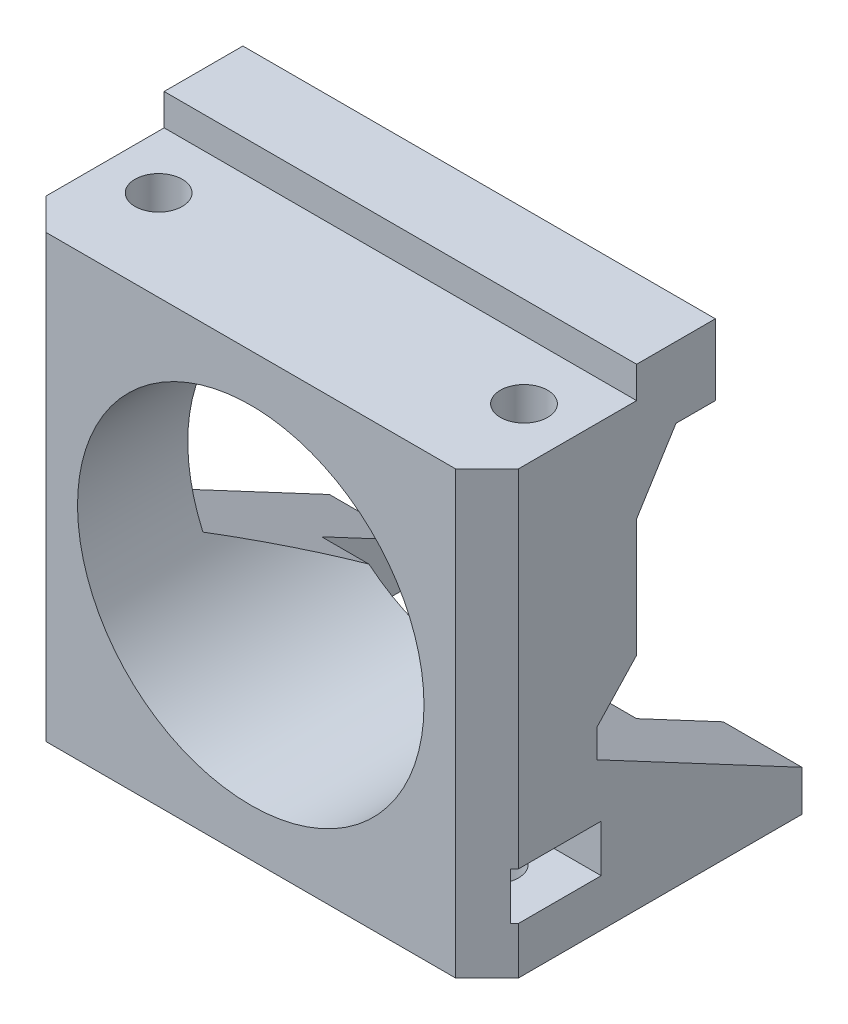
SolidWorks part; units mm, degrees
ref_plane "Front Plane" through (0, 0, 0) normal (0, 0, 1) x (1, 0, 0)
ref_plane "Top Plane" through (0, 0, 0) normal (0, 1, 0) x (1, 0, 0)
ref_plane "Right Plane" through (0, 0, 0) normal (1, 0, 0) x (0, 0, -1)
sketch "Sketch1" plane through (0, 0, 0) normal (0, 0, 1) x (1, 0, 0)
  line L1 (-15, 14) -> (15, 14)
  line L2 (-15, 14) -> (-15, -14)
  line L3 (-15, -14) -> (15, -14)
  line L4 (15, 14) -> (15, -14)
  line L5 (-15, 14) -> (15, -14) construction
  line L6 (-15, -14) -> (15, 14) construction
  circle A0 centre (0, 0) radius 11
  dimension "D1" = 22
  dimension "D2" = 30
  dimension "D3" = 28
extrude "Boss-Extrude1" add sketch "Sketch1" along normal blind 7
sketch "Sketch2" plane through (0, 0, 0) normal (0, 0, -1) x (-1, 0, 0)
  line L0 (0, 0) -> (0, -50000) construction
  line L1 (-15, -14) -> (-10, -14)
  line L2 (-15, -14) -> (-15, -11.5)
  line L3 (-15, -11.5) -> (-10, -11.5)
  line L4 (-10, -14) -> (-10, -11.5)
  line L5 (15, -11.5) -> (10, -11.5)
  line L6 (10, -14) -> (10, -11.5)
  line L7 (15, -14) -> (10, -14)
  line L8 (15, -14) -> (15, -11.5)
  dimension "D1" = 2.5
  dimension "D2" = 5
extrude "Boss-Extrude2" add sketch "Sketch2" along normal blind 13 contours L5 L6 L7 L8 | L2 L3 L4 L1
chamfer "Chamfer2" distance 2 angle 45 2 edges at (-10, -12.75, 0) (10, -12.75, 0)
sketch "Sketch5" plane through (0, -14, 0) normal (0, -1, 0) x (1, 0, 0)
  line L0 (-10, -7.5) -> (10, -7.5)
  line L1 (-10, -13) -> (-10, -2) construction
  line L2 (10, -13) -> (10, -2) construction
  line L3 (10, -7.5) -> (10, -2)
  line L4 (10, -2) -> (8, 0)
  line L5 (8, 0) -> (-8, 0)
  line L6 (-8, 0) -> (-10, -2)
  line L7 (-10, -2) -> (-10, -7.5)
  line M5 (-10, -13) -> (-10, -2)
  line M6 (-10, -2) -> (-8, 0)
  line M7 (-8, 0) -> (8, 0)
  line M8 (8, 0) -> (10, -2)
  line M9 (10, -2) -> (10, -13)
extrude "Boss-Extrude6" add sketch "Sketch5" against normal up to surface (2.5 mm away) contours L0 M5 M9 M8 M7 M6 region at (0, -14, -3.8345) up to face at (11.6, -11.5, -5.6)
chamfer "Chamfer3" distance 2 angle 45 1 edges at (15, 0, 7)
chamfer "Chamfer4" distance 2 angle 45 1 edges at (-15, 0, 7)
sketch "Sketch4" plane through (0, 0, 0) normal (0, 0, -1) x (-1, 0, 0)
  line L1 (-15, -11.5) -> (-15, 14) construction
  line L2 (-15, 14) -> (15, 14) construction
  line L3 (15, 14) -> (15, -11.5) construction
  line L8 (0, 0) -> (0, 50000) construction
  line L14 (-15, 0) -> (15, 11.5)
  line L15 (15, 11.5) -> (15, 14)
  line L16 (15, 14) -> (-15, 14)
  line L18 (-15, 14) -> (-15, 0)
  line L19 (-15, 14) -> (-15, -14) construction
  point P8 (-15, 0)
  dimension "D1" = 2.5
extrude "Boss-Extrude4" add sketch "Sketch4" along normal blind 2.5
chamfer "Chamfer6" distance 2.5 2 edges at (12.9432, 0.7884, 0) (-11.0214, 9.9749, 0)
chamfer "Chamfer7" distance 7 angle 62 1 edges at (0, -11.5, 0) first distance on face at (-0.4851, -4.0745, 0)
sketch "Sketch7" plane through (0, -14, 0) normal (0, -1, 0) x (1, 0, 0)
  circle A0 centre (11, 2.5) radius 2 construction
  circle A1 centre (-11, 2.5) radius 2 construction
  circle A2 centre (11, 2.5) radius 2 construction
  circle A3 centre (-11, 2.5) radius 2 construction
  circle A4 centre (-11, 2.5) radius 1.5
  circle A5 centre (11, 2.5) radius 1.5
  dimension "D1" = 3
  dimension "D2" = 3
extrude "Cut-Extrude2" cut sketch "Sketch7" against normal blind 6.4
sketch "Sketch8" plane through (0, 14, 0) normal (0, 1, 0) x (1, 0, 0)
  line L0 (-15, 2.5) -> (15, 2.5)
  line L1 (-15, -5) -> (-15, 2.5) construction
  line L2 (15, 2.5) -> (15, 7.5)
  line L3 (15, 7.5) -> (-15, 7.5)
  line L4 (-15, 7.5) -> (-15, 2.5)
  line L5 (15, -5) -> (15, 2.5) construction
  line L6 (-15, 2.5) -> (15, 2.5) construction
  dimension "D1" = 5
extrude "Boss-Extrude7" add sketch "Sketch8" along normal up to surface (4.5 mm away) from offset 2.5 offset against normal yes
chamfer "Chamfer8" distance 2.5 angle 58 1 edges at (0, 11.5, -2.5) first distance on face at (0, 11.5, -5)
sketch "Sketch9" plane through (0, -14, 0) normal (0, -1, 0) x (1, 0, 0)
  line L0 (-13, 7) -> (13, 7) construction
  line L1 (7.8246, 2.5) -> (9.4123, -0.25)
  line L2 (9.4123, -0.25) -> (12.5877, -0.25)
  line L3 (12.5877, -0.25) -> (14.1754, 2.5)
  line L4 (14.1754, 2.5) -> (12.5877, 5.25)
  line L5 (12.5877, 5.25) -> (9.4123, 5.25)
  line L6 (9.4123, 5.25) -> (7.8246, 2.5)
  line L7 (-7.8246, 2.5) -> (-9.4123, 5.25)
  line L8 (-9.4123, 5.25) -> (-12.5877, 5.25)
  line L9 (-12.5877, 5.25) -> (-14.1754, 2.5)
  line L10 (-14.1754, 2.5) -> (-12.5877, -0.25)
  line L11 (-12.5877, -0.25) -> (-9.4123, -0.25)
  line L12 (-9.4123, -0.25) -> (-7.8246, 2.5)
  circle A0 centre (11, 2.5) radius 1.5 construction
  circle A1 centre (-11, 2.5) radius 1.5 construction
  circle A2 centre (11, 2.5) radius 1.5
  circle A3 centre (-11, 2.5) radius 1.5
  circle A4 centre (11, 2.5) radius 2.75 construction
  circle A5 centre (-11, 2.5) radius 2.75 construction
  dimension "D1" = 5.5
extrude "Cut-Extrude3" cut sketch "Sketch9" against normal blind 3 from offset 3 offset against normal yes
sketch "Sketch10" plane through (15, 0, 0) normal (1, 0, 0) x (0, 0, -1)
  line L0 (-5.25, -8) -> (-5.25, -11) construction
  line L1 (0.25, -8) -> (0.25, -11) construction
  line L2 (-5.25, -8) -> (-5.25, -11)
  line L3 (0.25, -8) -> (0.25, -11)
  line L4 (-5.25, -8) -> (0.25, -8)
  line L5 (-5.25, -11) -> (0.25, -11)
extrude "Cut-Extrude4" cut sketch "Sketch10" against normal blind 5.6
extrude "Cut-Extrude5" cut sketch "Sketch10<2>" along normal blind 5.6 from surface starting at face at (-15, 4.3555, -3.5)
sketch "Sketch10<2>" plane through (15, 0, 0) normal (1, 0, 0) x (0, 0, -1) same geometry as "Sketch10"
hole_wizard "Ø1.0mm Dowel Hole1" positions "Sketch15" profile "Sketch16" hole size "Ø1.0" standard "ANSI Metric"
sketch "Sketch15" plane through (0, 14, 0) normal (0, 1, 0) x (1, 0, 0)
  point P0 (-11.6, -1.25)
  point P3 (11.6, -1.25)
sketch "Sketch16" plane through (-11.6, 14, 1.25) normal (1, 0, 0) x (0, 0, 1)
  line L0 (0, 0) -> (0, 8)
  line L1 (0, 8) -> (1.5, 7.0987)
  line L2 (1.5, 7.0987) -> (1.5, 0)
  line L5 (1.5, 0) -> (0, 0)
  line L10 (0, 8) -> (-1.5, 7.0987) construction
  line L11 (0, -6.35) -> (0, 107.95) construction
  dimension "Hole Dia." = 3
  dimension "Hole Depth" = 8
  dimension "Drill Angle" = 118
